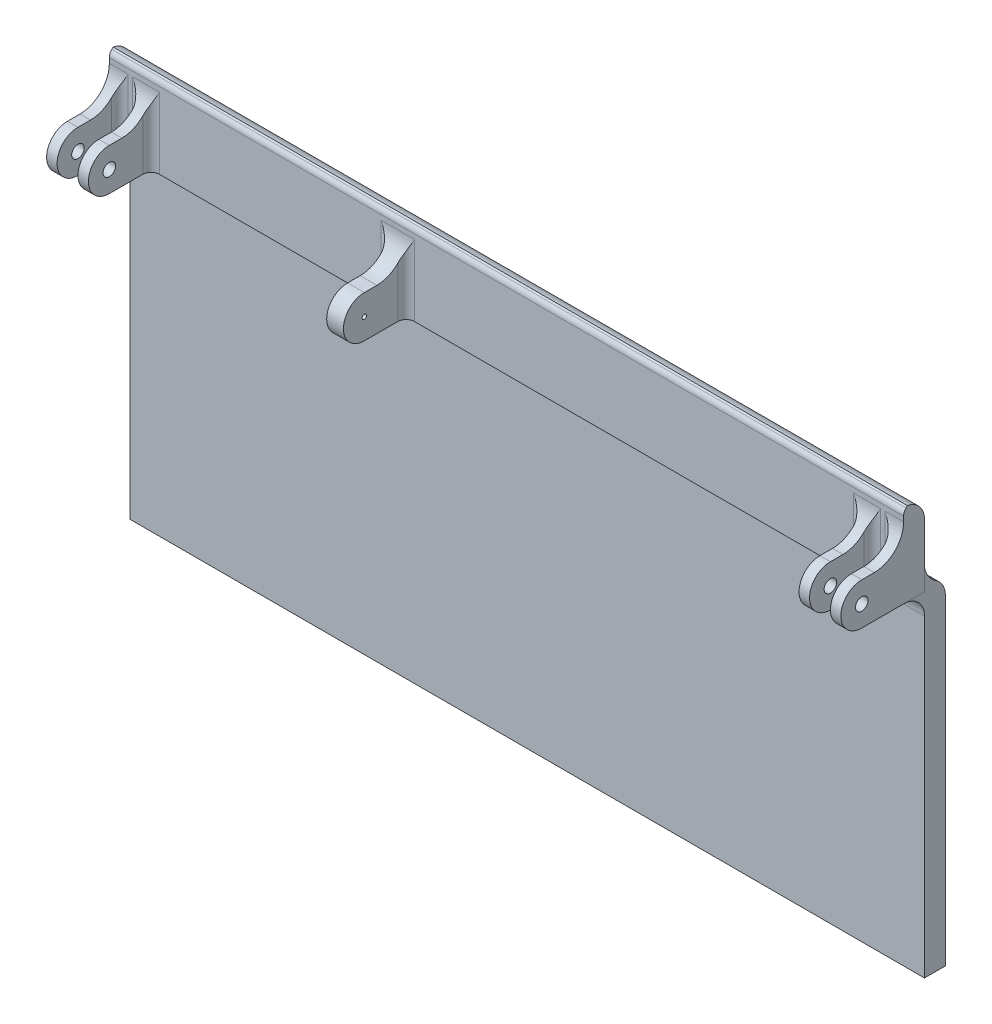
SolidWorks part; units mm, degrees
ref_plane "Plan de face" through (0, 0, 0) normal (0, 0, 1) x (1, 0, 0)
ref_plane "Plan de dessus" through (0, 0, 0) normal (0, 1, 0) x (1, 0, 0)
ref_plane "Plan de droite" through (0, 0, 0) normal (1, 0, 0) x (0, 0, -1)
sketch "Esquisse1" plane through (0, 0, 0) normal (0, 0, 1) x (1, 0, 0)
  line L1 (-95, 10) -> (95, 10)
  line L2 (-95, 10) -> (-95, -10)
  line L3 (-95, -10) -> (95, -10)
  line L4 (95, 10) -> (95, -10)
  line L5 (-95, 10) -> (95, -10) construction
  line L6 (-95, -10) -> (95, 10) construction
  point P0 (0, 0)
  dimension "D1" = 20
  dimension "D2" = 190
extrude "Boss.-Extru.1" add sketch "Esquisse1" along normal blind 5
sketch "Esquisse2" plane through (-95, 0, 0) normal (-1, 0, 0) x (0, 0, 1)
  line L0 (5, -10) -> (15, -10)
  line L1 (15, -10) -> (15, 0) construction
  line L2 (15, 0) -> (5, 0)
  line L3 (5, 10) -> (5, -10) construction
  line L4 (5, 0) -> (5, -10)
  arc A0 (15, 0) -> (15, -10) centre (15, -5) cw
  circle A1 centre (15, -5) radius 0.525
  dimension "D3" = 1.05
  dimension "D1" = 10
  dimension "D2" = 10
extrude "Boss.-Extru.2" add sketch "Esquisse2" against normal blind 4 from offset 67 offset against normal yes
sketch "Esquisse3" plane through (-95, 0, 0) normal (-1, 0, 0) x (0, 0, 1)
  line L1 (5, -10) -> (0, -10)
  line L2 (0, -15) -> (0, -90)
  line L3 (0, -90) -> (-5, -90)
  line L4 (-5, -90) -> (-5, -10)
  line L5 (0, 10) -> (0, -10) construction
  line L6 (0, -5) -> (0, -10)
  line L7 (5, 10) -> (5, -10) construction
  line L8 (5, -10) -> (0, -10) construction
  arc A0 (-5, -10) -> (0, -5) centre (-6.3568, -3.6432) ccw
  arc A1 (5, -10) -> (0, -15) centre (5, -15) ccw
  point P4 (0, 0)
  point P10 (2.5, -10)
  point P12 (0, 0)
  point P15 (0, -7.6533)
  point P16 (0, -5.2176)
  point P17 (0, 0)
  point P18 (0, -4.2963)
  point P19 (2.5, -10)
  point P20 (2.5, -10)
  point P21 (0, 0)
  point P22 (5.0001, -10)
  point P23 (0, 0)
  point P24 (4.9467, -10)
  point P25 (0, 0)
  dimension "D3" = 6.5
  dimension "D4" = 5
  dimension "D1" = 5
  dimension "D2" = 80
extrude "Boss.-Extru.3" add sketch "Esquisse3" against normal through all separate body
fillet "Congé3" radius 5 1 edges at (0, -10, -5)
fillet "Congé4" radius 5 1 edges at (0, 10, 0)
chamfer "Chanfrein1" distance 1 angle 45 1 edges at (0, 10, 5)
sketch "Esquisse6" plane through (-95, 0, 0) normal (-1, 0, 0) x (0, 0, 1)
  line L3 (5, 0) -> (5, -10)
  line L4 (5, 0) -> (5, -10)
  line L10 (5, -10) -> (15, -10)
  line L12 (5, -10) -> (15, -10)
  line L13 (15, 0) -> (5, 0)
  line L14 (15, 0) -> (5, 0)
  circle A0 centre (15, -5) radius 1.5
  arc A1 (15, -10) -> (15, 0) centre (15, -5) ccw
  arc A5 (15, -10) -> (15, 0) centre (15, -5) ccw
  dimension "D2" = 3
  dimension "D1" = 0
extrude "Boss.-Extru.4" add sketch "Esquisse6" against normal blind 2.5
sketch "Esquisse7" plane through (-92.5, 0, 0) normal (1, 0, 0) x (0, 0, -1)
  line L3 (-5, 0) -> (-15, 0)
  line L5 (-5, 0) -> (-15, 0)
  line L10 (-15, -10) -> (-5, -10)
  line L12 (-15, -10) -> (-5, -10)
  line L13 (-5, -10) -> (-5, 0)
  line L14 (-5, -10) -> (-5, 0)
  circle A0 centre (-15, -5) radius 1.5 construction
  arc A1 (-15, 0) -> (-15, -10) centre (-15, -5) ccw
  circle A3 centre (-15, -5) radius 1.5
  arc A6 (-15, 0) -> (-15, -10) centre (-15, -5) ccw
  dimension "D1" = 0
extrude "Boss.-Extru.5" add sketch "Esquisse7" along normal blind 2.5 from offset 5
mirror "Symétrie2" about plane through (0, 0, 0) normal (1, 0, 0) of "Boss.-Extru.4", "Boss.-Extru.5"
fillet "Congé5" radius 7 5 edges at (93.75, 0, 5) (86.25, 0, 5) (-26, 0, 5) (-86.25, 0, 5) (-93.75, 0, 5)
fillet "Congé6" radius 2 8 edges at (-24, -1.5, 5) (-28, -1.5, 5) (92.5, -1.5, 5) (87.5, -1.5, 5) (85, -1.5, 5) (-87.5, -1.5, 5) (-92.5, -1.5, 5) (-85, -1.5, 5)
fillet "Congé7" radius 2 1 edges at (0, 9, 5)
